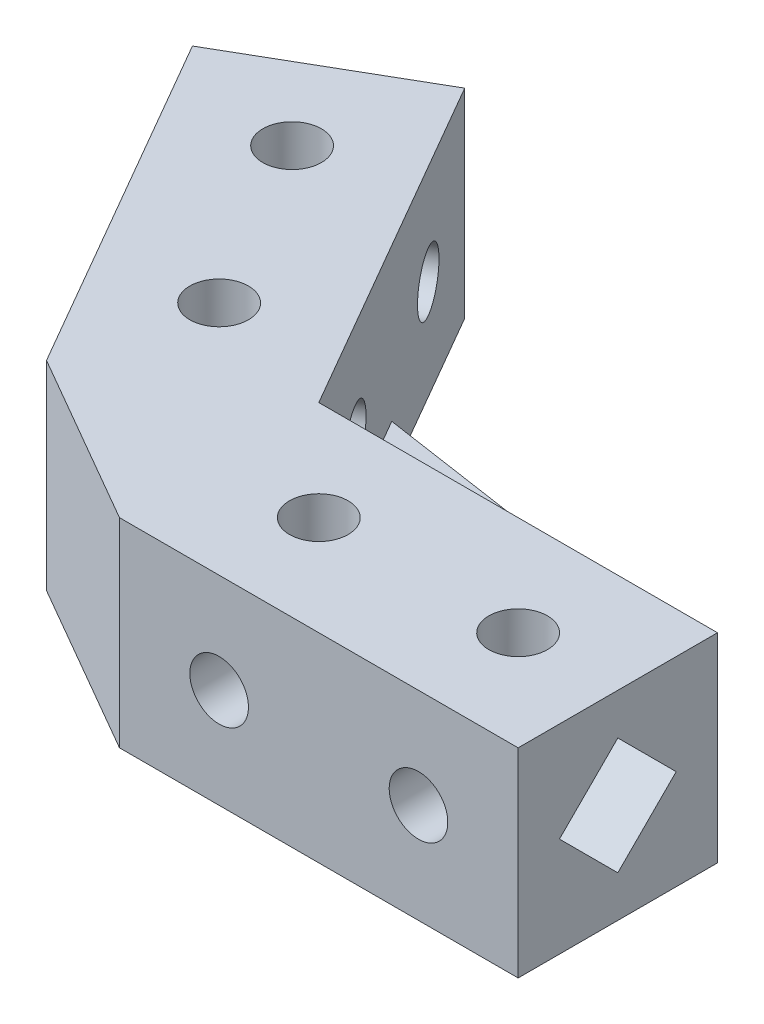
SolidWorks part; units mm, degrees
ref_plane "Front Plane" through (0, 0, 0) normal (0, 0, 1) x (1, 0, 0)
ref_plane "Top Plane" through (0, 0, 0) normal (0, 1, 0) x (1, 0, 0)
ref_plane "Right Plane" through (0, 0, 0) normal (1, 0, 0) x (0, 0, -1)
other "Configuration Table"
sketch "sketch1" plane through (0, 0, 0) normal (0, 1, 0) x (1, 0, 0)
  line L0 (0, -8.5) -> (8.5, -8.5) construction
  line L1 (0, 0) -> (34, 0)
  line L2 (0, 0) -> (0, -17)
  line L3 (0, -17) -> (34, -17)
  line L4 (34, 0) -> (34, -17)
  line L5 (8.5, -8.5) -> (25.5, -8.5) construction
  circle A1 centre (8.5, -8.5) radius 2.5
  circle A2 centre (25.5, -8.5) radius 2.5
  dimension "D4" = 5
  dimension "D1" = 17
  dimension "D2" = 34
  dimension "D3" = 8.5
  dimension "D6" = 17
extrude "Boss-Extrude1" add sketch "sketch1" along normal blind 17
sketch "Sketch6" plane through (0, 0, 0) normal (0, 0, -1) x (-1, 0, 0)
  line L0 (-34, 8.5) -> (-25.5, 8.5) construction
  line L1 (-25.5, 8.5) -> (-8.5, 8.5) construction
  line L4 (-34, 0) -> (0, 0)
  line L5 (0, 0) -> (0, 17)
  line L6 (0, 17) -> (-34, 17)
  line L7 (-34, 17) -> (-34, 0)
  line L8 (-34, 0) -> (0, 0)
  line L9 (0, 0) -> (0, 17)
  line L10 (0, 17) -> (-34, 17)
  line L11 (-34, 17) -> (-34, 0)
  circle A0 centre (-25.5, 8.5) radius 2.5
  circle A1 centre (-8.5, 8.5) radius 2.5
  dimension "D3" = 5
  dimension "D2" = 8.5
  dimension "D5" = 17
extrude "Cut-Extrude10" cut sketch "Sketch6" against normal through all flip side to cut
sketch "Sketch7" plane through (34, 0, 0) normal (1, 0, 0) x (0, 0, -1)
  line L0 (-17, 8.5) -> (0, 8.5) construction
  line L1 (-8.5, 8.5) -> (-8.5, 13.478) construction
  line L2 (-8.5, 13.478) -> (-3.522, 8.5)
  line L3 (-3.522, 8.5) -> (-8.5, 3.522)
  line L4 (-17, 0) -> (0, 0)
  line L5 (0, 0) -> (0, 17)
  line L6 (0, 17) -> (-17, 17)
  line L7 (-17, 17) -> (-17, 0)
  line L8 (-17, 0) -> (0, 0)
  line L9 (0, 0) -> (0, 17)
  line L10 (0, 17) -> (-17, 17)
  line L11 (-17, 17) -> (-17, 0)
  line L12 (-8.5, 3.522) -> (-13.478, 8.5)
  line L13 (-13.478, 8.5) -> (-8.5, 13.478)
  dimension "D2" = 7.04
extrude "Cut-Extrude11" cut sketch "Sketch7" against normal blind 17 flip side to cut
sketch "Sketch9" plane through (0, 0, 0) normal (0, 1, 0) x (1, 0, 0)
  line L0 (0, 0) -> (34, 0) construction
  line L1 (0, 0) -> (17, 29.4449) construction
  dimension "D1" = 60
ref_plane "Plane2" through (0, 0, 0) normal (-0.866, 0, -0.5) x (-0.5, 0, 0.866)
mirror "Mirror6" about plane through (0, 0, 0) normal (-0.866, 0, -0.5) of bodies 118 110
sketch "Sketch11" plane through (0, 0, 0) normal (0, 1, 0) x (1, 0, 0)
  line L0 (-14.7224, -8.5) -> (0, -17)
  line L1 (0, 0) -> (-14.7224, -8.5) construction
  line L2 (0, 0) -> (0, -17) construction
  line L3 (0, 0) -> (-14.7224, -8.5)
  line L4 (0, 0) -> (0, -17)
extrude "Boss-Extrude2" add sketch "Sketch11" along normal blind 17
sketch "Sketch13" plane through (0, 0, 0) normal (0, 1, 0) x (1, 0, 0)
  line L0 (-11.6112, 3.1112) -> (4.6528, 8.059) construction
  line L1 (0, 0) -> (17, 29.4449) construction
  line L2 (4.6528, 8.059) -> (8.5, -8.5) construction
  line L4 (7.1528, 12.3891) -> (-8.5, 14.7224)
  line L5 (-17, 29.4449) -> (0, 0) construction
  line L6 (7.1528, 12.3891) -> (17, 0)
  line L7 (0, 0) -> (34, 0) construction
  line L8 (0, 0) -> (17, 29.4449) construction
  line L9 (-8.5, 14.7224) -> (0, 0)
  line L10 (0, 0) -> (17, 0)
  circle A0 centre (8.5, -8.5) radius 2.5 construction
  circle A1 centre (-11.6112, 3.1112) radius 2.5 construction
  circle A2 centre (8.5, -8.5) radius 2.5 construction
  circle A3 centre (-11.6112, 3.1112) radius 2.5 construction
  circle A4 centre (4.6528, 8.059) radius 2.5
  dimension "D1" = 17
  dimension "D3" = 5
  dimension "D2" = 5
  dimension "D4" = 17
extrude "Boss-Extrude3" add sketch "Sketch13" along normal blind 4
equation "\"D2@sketch1\" = \"length\""
equation "\"holes\"= 2'Holes per side"
equation "\"cdist\"= 17mm'centre distance between holes"
equation "\"width\"= 17mm"
equation "\"length\"= \"cdist\" * \"holes\""
equation "\"D1@sketch1\"=\"width\""
equation "\"hdiam\"= 5mm'Hole diametre"
equation "\"D4@sketch1\" = \"hdiam\""
equation "\"D6@sketch1\" = \"cdist\""
equation "\"D5@sketch1\" = \"holes\""
equation "\"D2@Sketch6\"=\"cdist\"/2"
equation "\"D3@Sketch6\"=\"hdiam\""
equation "\"D5@Sketch6\"=\"cdist\""
equation "\"D4@Sketch6\"=\"holes\""
equation "\"D1@Boss-Extrude1\"=\"width\""
equation "\"joint\"= 120"
equation "\"D1@Sketch9\"=\"joint\"/2"
equation "\"D1@Boss-Extrude2\"=\"width\""
equation "\"D2@Sketch13\"=\"hdiam\""
equation "\"D4@Sketch13\"=\"cdist\""
equation "\"D1@Boss-Extrude3\"=\"supportheight\""
equation "\"supportheight\"= 4mm"
equation "\"tolerance\"= 0.04mm"
equation "\"insetwidth\"= 7mm"
equation "\"D2@Sketch7\"=\"insetwidth\"+\"tolerance\""
equation "\"D1@Cut-Extrude11\"=\"cdist\""
equation "\"true\"= 1"
equation "\"false\"= 0"
equation "\"centresupport\"= \"true\""
equation "\"Boss-Extrude3\"= IIF ( \"centresupport\" < \"true\" , \"suppressed\" , \"unsuppressed\" )"
